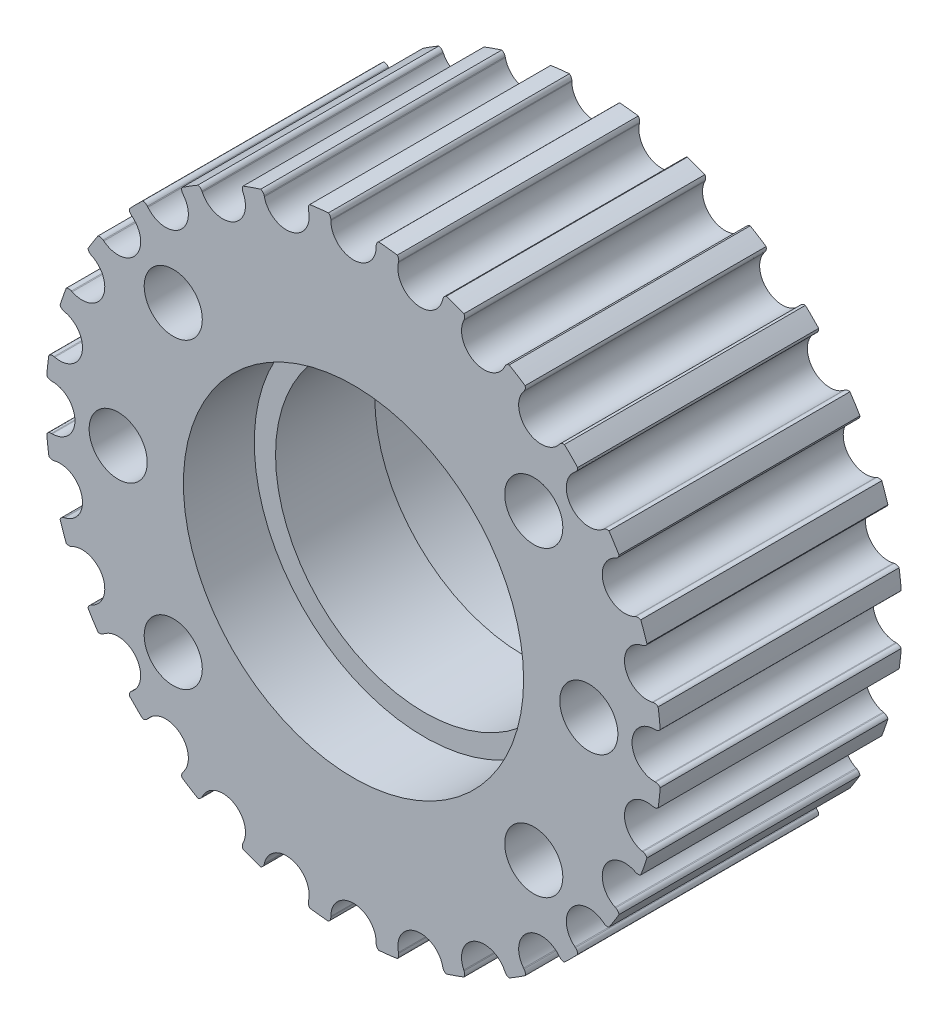
SolidWorks part; units mm, degrees
ref_plane "Front Plane" through (0, 0, 0) normal (0, 0, 1) x (1, 0, 0)
ref_plane "Top Plane" through (0, 0, 0) normal (0, 1, 0) x (1, 0, 0)
ref_plane "Right Plane" through (0, 0, 0) normal (1, 0, 0) x (0, 0, -1)
sketch "Sketch1" plane through (0, 0, 0) normal (0, 0, 1) x (1, 0, 0)
  line L0 (3.182, 21.1317) -> (3.1687, 21.0733)
  line L1 (6.2885, 20.3612) -> (6.3018, 20.4197)
  line L2 (7.8045, 19.8939) -> (7.7785, 19.8398)
  line L3 (10.6616, 18.4514) -> (10.6876, 18.5054)
  line L4 (-1.6, 21.31) -> (-1.6, 21.25)
  line L5 (1.6, 21.25) -> (1.6, 21.31)
  line L6 (12.0356, 17.6584) -> (11.9982, 17.6115)
  line L7 (14.5001, 15.6163) -> (14.5375, 15.6632)
  line L8 (15.6632, 14.5375) -> (15.6163, 14.5001)
  line L9 (17.6115, 11.9982) -> (17.6584, 12.0356)
  line L10 (18.5054, 10.6876) -> (18.4514, 10.6616)
  line L11 (19.8398, 7.7785) -> (19.8939, 7.8045)
  line L12 (20.4197, 6.3018) -> (20.3612, 6.2885)
  line L13 (21.0733, 3.1687) -> (21.1317, 3.182)
  line L14 (21.31, 1.6) -> (21.25, 1.6)
  line L15 (21.25, -1.6) -> (21.31, -1.6)
  line L16 (21.1317, -3.182) -> (21.0733, -3.1687)
  line L17 (20.3612, -6.2885) -> (20.4197, -6.3018)
  line L18 (19.8939, -7.8045) -> (19.8398, -7.7785)
  line L19 (18.4514, -10.6616) -> (18.5054, -10.6876)
  line L20 (17.6584, -12.0356) -> (17.6115, -11.9982)
  line L21 (15.6163, -14.5001) -> (15.6632, -14.5375)
  line L22 (14.5375, -15.6632) -> (14.5001, -15.6163)
  line L23 (11.9982, -17.6115) -> (12.0356, -17.6584)
  line L24 (10.6876, -18.5054) -> (10.6616, -18.4514)
  line L25 (7.7785, -19.8398) -> (7.8045, -19.8939)
  line L26 (6.3018, -20.4197) -> (6.2885, -20.3612)
  line L27 (3.1687, -21.0733) -> (3.182, -21.1317)
  line L28 (1.6, -21.31) -> (1.6, -21.25)
  line L29 (-1.6, -21.25) -> (-1.6, -21.31)
  line L30 (-3.182, -21.1317) -> (-3.1687, -21.0733)
  line L31 (-6.2885, -20.3612) -> (-6.3018, -20.4197)
  line L32 (-7.8045, -19.8939) -> (-7.7785, -19.8398)
  line L33 (-10.6616, -18.4514) -> (-10.6876, -18.5054)
  line L34 (-12.0356, -17.6584) -> (-11.9982, -17.6115)
  line L35 (-14.5001, -15.6163) -> (-14.5375, -15.6632)
  line L36 (-15.6632, -14.5375) -> (-15.6163, -14.5001)
  line L37 (-17.6115, -11.9982) -> (-17.6584, -12.0356)
  line L38 (-18.5054, -10.6876) -> (-18.4514, -10.6616)
  line L39 (-19.8398, -7.7785) -> (-19.8939, -7.8045)
  line L40 (-20.4197, -6.3018) -> (-20.3612, -6.2885)
  line L41 (-21.0733, -3.1687) -> (-21.1317, -3.182)
  line L42 (-21.31, -1.6) -> (-21.25, -1.6)
  line L43 (-21.25, 1.6) -> (-21.31, 1.6)
  line L44 (-21.1317, 3.182) -> (-21.0733, 3.1687)
  line L45 (-20.3612, 6.2885) -> (-20.4197, 6.3018)
  line L46 (-19.8939, 7.8045) -> (-19.8398, 7.7785)
  line L47 (-18.4514, 10.6616) -> (-18.5054, 10.6876)
  line L48 (-17.6584, 12.0356) -> (-17.6115, 11.9982)
  line L49 (-15.6163, 14.5001) -> (-15.6632, 14.5375)
  line L50 (-14.5375, 15.6632) -> (-14.5001, 15.6163)
  line L51 (-11.9982, 17.6115) -> (-12.0356, 17.6584)
  line L52 (-10.6876, 18.5054) -> (-10.6616, 18.4514)
  line L53 (-7.7785, 19.8398) -> (-7.8045, 19.8939)
  line L54 (-6.3018, 20.4197) -> (-6.2885, 20.3612)
  line L55 (-3.1687, 21.0733) -> (-3.182, 21.1317)
  arc A2 (-1.7706, 21.6377) -> (-3.0886, 21.4892) centre (0, 0) ccw
  arc A3 (3.0886, 21.4892) -> (1.7706, 21.6377) centre (0, 0) ccw
  arc A4 (3.0886, 21.4892) -> (1.7706, 21.6377) centre (0, 0) ccw
  arc A5 (7.793, 20.2631) -> (6.541, 20.7012) centre (0, 0) ccw
  arc A6 (6.541, 20.7012) -> (6.3018, 20.4197) centre (6.6918, 20.3307) ccw
  arc A7 (6.541, 20.7012) -> (3.0886, 21.4892) centre (0, 0) ccw
  arc A8 (1.7706, 21.6377) -> (1.6, 21.31) centre (2, 21.31) ccw
  arc A9 (1.7706, 21.6377) -> (-1.7706, 21.6377) centre (0, 0) ccw
  arc A10 (-1.6, 21.31) -> (-1.7706, 21.6377) centre (-2, 21.31) ccw
  arc A11 (-1.6, 21.25) -> (1.6, 21.25) centre (0, 21.25) ccw
  arc A12 (3.182, 21.1317) -> (3.0886, 21.4892) centre (2.7921, 21.2208) ccw
  arc A13 (3.1687, 21.0733) -> (6.2885, 20.3612) centre (4.7286, 20.7172) ccw
  arc A14 (7.793, 20.2631) -> (6.541, 20.7012) centre (0, 0) ccw
  arc A15 (12.1066, 18.021) -> (10.9835, 18.7266) centre (0, 0) ccw
  arc A16 (10.9835, 18.7266) -> (10.6876, 18.5054) centre (11.048, 18.3319) ccw
  arc A17 (10.9835, 18.7266) -> (7.793, 20.2631) centre (0, 0) ccw
  arc A18 (7.8045, 19.8939) -> (7.793, 20.2631) centre (7.4441, 20.0674) ccw
  arc A19 (7.7785, 19.8398) -> (10.6616, 18.4514) centre (9.22, 19.1456) ccw
  arc A20 (12.1066, 18.021) -> (10.9835, 18.7266) centre (0, 0) ccw
  arc A21 (15.8131, 14.8752) -> (14.8752, 15.8131) centre (0, 0) ccw
  arc A22 (14.8752, 15.8131) -> (14.5375, 15.6632) centre (14.8502, 15.4138) ccw
  arc A23 (14.8752, 15.8131) -> (12.1066, 18.021) centre (0, 0) ccw
  arc A24 (12.0356, 17.6584) -> (12.1066, 18.021) centre (11.7229, 17.9078) ccw
  arc A25 (11.9982, 17.6115) -> (14.5001, 15.6163) centre (13.2492, 16.6139) ccw
  arc A26 (15.8131, 14.8752) -> (14.8752, 15.8131) centre (0, 0) ccw
  arc A27 (18.7266, 10.9835) -> (18.021, 12.1066) centre (0, 0) ccw
  arc A28 (18.021, 12.1066) -> (17.6584, 12.0356) centre (17.9078, 11.7229) ccw
  arc A29 (18.021, 12.1066) -> (15.8131, 14.8752) centre (0, 0) ccw
  arc A30 (15.6632, 14.5375) -> (15.8131, 14.8752) centre (15.4138, 14.8502) ccw
  arc A31 (15.6163, 14.5001) -> (17.6115, 11.9982) centre (16.6139, 13.2492) ccw
  arc A32 (18.7266, 10.9835) -> (18.021, 12.1066) centre (0, 0) ccw
  arc A33 (20.7012, 6.541) -> (20.2631, 7.793) centre (0, 0) ccw
  arc A34 (20.2631, 7.793) -> (19.8939, 7.8045) centre (20.0674, 7.4441) ccw
  arc A35 (20.2631, 7.793) -> (18.7266, 10.9835) centre (0, 0) ccw
  arc A36 (18.5054, 10.6876) -> (18.7266, 10.9835) centre (18.3319, 11.048) ccw
  arc A37 (18.4514, 10.6616) -> (19.8398, 7.7785) centre (19.1456, 9.22) ccw
  arc A38 (20.7012, 6.541) -> (20.2631, 7.793) centre (0, 0) ccw
  arc A39 (21.6377, 1.7706) -> (21.4892, 3.0886) centre (0, 0) ccw
  arc A40 (21.4892, 3.0886) -> (21.1317, 3.182) centre (21.2208, 2.7921) ccw
  arc A41 (21.4892, 3.0886) -> (20.7012, 6.541) centre (0, 0) ccw
  arc A42 (20.4197, 6.3018) -> (20.7012, 6.541) centre (20.3307, 6.6918) ccw
  arc A43 (20.3612, 6.2885) -> (21.0733, 3.1687) centre (20.7172, 4.7286) ccw
  arc A44 (21.6377, 1.7706) -> (21.4892, 3.0886) centre (0, 0) ccw
  arc A45 (21.4892, -3.0886) -> (21.6377, -1.7706) centre (0, 0) ccw
  arc A46 (21.6377, -1.7706) -> (21.31, -1.6) centre (21.31, -2) ccw
  arc A47 (21.6377, -1.7706) -> (21.6377, 1.7706) centre (0, 0) ccw
  arc A48 (21.31, 1.6) -> (21.6377, 1.7706) centre (21.31, 2) ccw
  arc A49 (21.25, 1.6) -> (21.25, -1.6) centre (21.25, 0) ccw
  arc A50 (21.4892, -3.0886) -> (21.6377, -1.7706) centre (0, 0) ccw
  arc A51 (20.2631, -7.793) -> (20.7012, -6.541) centre (0, 0) ccw
  arc A52 (20.7012, -6.541) -> (20.4197, -6.3018) centre (20.3307, -6.6918) ccw
  arc A53 (20.7012, -6.541) -> (21.4892, -3.0886) centre (0, 0) ccw
  arc A54 (21.1317, -3.182) -> (21.4892, -3.0886) centre (21.2208, -2.7921) ccw
  arc A55 (21.0733, -3.1687) -> (20.3612, -6.2885) centre (20.7172, -4.7286) ccw
  arc A56 (20.2631, -7.793) -> (20.7012, -6.541) centre (0, 0) ccw
  arc A57 (18.021, -12.1066) -> (18.7266, -10.9835) centre (0, 0) ccw
  arc A58 (18.7266, -10.9835) -> (18.5054, -10.6876) centre (18.3319, -11.048) ccw
  arc A59 (18.7266, -10.9835) -> (20.2631, -7.793) centre (0, 0) ccw
  arc A60 (19.8939, -7.8045) -> (20.2631, -7.793) centre (20.0674, -7.4441) ccw
  arc A61 (19.8398, -7.7785) -> (18.4514, -10.6616) centre (19.1456, -9.22) ccw
  arc A62 (18.021, -12.1066) -> (18.7266, -10.9835) centre (0, 0) ccw
  arc A63 (14.8752, -15.8131) -> (15.8131, -14.8752) centre (0, 0) ccw
  arc A64 (15.8131, -14.8752) -> (15.6632, -14.5375) centre (15.4138, -14.8502) ccw
  arc A65 (15.8131, -14.8752) -> (18.021, -12.1066) centre (0, 0) ccw
  arc A66 (17.6584, -12.0356) -> (18.021, -12.1066) centre (17.9078, -11.7229) ccw
  arc A67 (17.6115, -11.9982) -> (15.6163, -14.5001) centre (16.6139, -13.2492) ccw
  arc A68 (14.8752, -15.8131) -> (15.8131, -14.8752) centre (0, 0) ccw
  arc A69 (10.9835, -18.7266) -> (12.1066, -18.021) centre (0, 0) ccw
  arc A70 (12.1066, -18.021) -> (12.0356, -17.6584) centre (11.7229, -17.9078) ccw
  arc A71 (12.1066, -18.021) -> (14.8752, -15.8131) centre (0, 0) ccw
  arc A72 (14.5375, -15.6632) -> (14.8752, -15.8131) centre (14.8502, -15.4138) ccw
  arc A73 (14.5001, -15.6163) -> (11.9982, -17.6115) centre (13.2492, -16.6139) ccw
  arc A74 (10.9835, -18.7266) -> (12.1066, -18.021) centre (0, 0) ccw
  arc A75 (6.541, -20.7012) -> (7.793, -20.2631) centre (0, 0) ccw
  arc A76 (7.793, -20.2631) -> (7.8045, -19.8939) centre (7.4441, -20.0674) ccw
  arc A77 (7.793, -20.2631) -> (10.9835, -18.7266) centre (0, 0) ccw
  arc A78 (10.6876, -18.5054) -> (10.9835, -18.7266) centre (11.048, -18.3319) ccw
  arc A79 (10.6616, -18.4514) -> (7.7785, -19.8398) centre (9.22, -19.1456) ccw
  arc A80 (6.541, -20.7012) -> (7.793, -20.2631) centre (0, 0) ccw
  arc A81 (1.7706, -21.6377) -> (3.0886, -21.4892) centre (0, 0) ccw
  arc A82 (3.0886, -21.4892) -> (3.182, -21.1317) centre (2.7921, -21.2208) ccw
  arc A83 (3.0886, -21.4892) -> (6.541, -20.7012) centre (0, 0) ccw
  arc A84 (6.3018, -20.4197) -> (6.541, -20.7012) centre (6.6918, -20.3307) ccw
  arc A85 (6.2885, -20.3612) -> (3.1687, -21.0733) centre (4.7286, -20.7172) ccw
  arc A86 (1.7706, -21.6377) -> (3.0886, -21.4892) centre (0, 0) ccw
  arc A87 (-3.0886, -21.4892) -> (-1.7706, -21.6377) centre (0, 0) ccw
  arc A88 (-1.7706, -21.6377) -> (-1.6, -21.31) centre (-2, -21.31) ccw
  arc A89 (-1.7706, -21.6377) -> (1.7706, -21.6377) centre (0, 0) ccw
  arc A90 (1.6, -21.31) -> (1.7706, -21.6377) centre (2, -21.31) ccw
  arc A91 (1.6, -21.25) -> (-1.6, -21.25) centre (0, -21.25) ccw
  arc A92 (-3.0886, -21.4892) -> (-1.7706, -21.6377) centre (0, 0) ccw
  arc A93 (-7.793, -20.2631) -> (-6.541, -20.7012) centre (0, 0) ccw
  arc A94 (-6.541, -20.7012) -> (-6.3018, -20.4197) centre (-6.6918, -20.3307) ccw
  arc A95 (-6.541, -20.7012) -> (-3.0886, -21.4892) centre (0, 0) ccw
  arc A96 (-3.182, -21.1317) -> (-3.0886, -21.4892) centre (-2.7921, -21.2208) ccw
  arc A97 (-3.1687, -21.0733) -> (-6.2885, -20.3612) centre (-4.7286, -20.7172) ccw
  arc A98 (-7.793, -20.2631) -> (-6.541, -20.7012) centre (0, 0) ccw
  arc A99 (-12.1066, -18.021) -> (-10.9835, -18.7266) centre (0, 0) ccw
  arc A100 (-10.9835, -18.7266) -> (-10.6876, -18.5054) centre (-11.048, -18.3319) ccw
  arc A101 (-10.9835, -18.7266) -> (-7.793, -20.2631) centre (0, 0) ccw
  arc A102 (-7.8045, -19.8939) -> (-7.793, -20.2631) centre (-7.4441, -20.0674) ccw
  arc A103 (-7.7785, -19.8398) -> (-10.6616, -18.4514) centre (-9.22, -19.1456) ccw
  arc A104 (-12.1066, -18.021) -> (-10.9835, -18.7266) centre (0, 0) ccw
  arc A105 (-15.8131, -14.8752) -> (-14.8752, -15.8131) centre (0, 0) ccw
  arc A106 (-14.8752, -15.8131) -> (-14.5375, -15.6632) centre (-14.8502, -15.4138) ccw
  arc A107 (-14.8752, -15.8131) -> (-12.1066, -18.021) centre (0, 0) ccw
  arc A108 (-12.0356, -17.6584) -> (-12.1066, -18.021) centre (-11.7229, -17.9078) ccw
  arc A109 (-11.9982, -17.6115) -> (-14.5001, -15.6163) centre (-13.2492, -16.6139) ccw
  arc A110 (-15.8131, -14.8752) -> (-14.8752, -15.8131) centre (0, 0) ccw
  arc A111 (-18.7266, -10.9835) -> (-18.021, -12.1066) centre (0, 0) ccw
  arc A112 (-18.021, -12.1066) -> (-17.6584, -12.0356) centre (-17.9078, -11.7229) ccw
  arc A113 (-18.021, -12.1066) -> (-15.8131, -14.8752) centre (0, 0) ccw
  arc A114 (-15.6632, -14.5375) -> (-15.8131, -14.8752) centre (-15.4138, -14.8502) ccw
  arc A115 (-15.6163, -14.5001) -> (-17.6115, -11.9982) centre (-16.6139, -13.2492) ccw
  arc A116 (-18.7266, -10.9835) -> (-18.021, -12.1066) centre (0, 0) ccw
  arc A117 (-20.7012, -6.541) -> (-20.2631, -7.793) centre (0, 0) ccw
  arc A118 (-20.2631, -7.793) -> (-19.8939, -7.8045) centre (-20.0674, -7.4441) ccw
  arc A119 (-20.2631, -7.793) -> (-18.7266, -10.9835) centre (0, 0) ccw
  arc A120 (-18.5054, -10.6876) -> (-18.7266, -10.9835) centre (-18.3319, -11.048) ccw
  arc A121 (-18.4514, -10.6616) -> (-19.8398, -7.7785) centre (-19.1456, -9.22) ccw
  arc A122 (-20.7012, -6.541) -> (-20.2631, -7.793) centre (0, 0) ccw
  arc A123 (-21.6377, -1.7706) -> (-21.4892, -3.0886) centre (0, 0) ccw
  arc A124 (-21.4892, -3.0886) -> (-21.1317, -3.182) centre (-21.2208, -2.7921) ccw
  arc A125 (-21.4892, -3.0886) -> (-20.7012, -6.541) centre (0, 0) ccw
  arc A126 (-20.4197, -6.3018) -> (-20.7012, -6.541) centre (-20.3307, -6.6918) ccw
  arc A127 (-20.3612, -6.2885) -> (-21.0733, -3.1687) centre (-20.7172, -4.7286) ccw
  arc A128 (-21.6377, -1.7706) -> (-21.4892, -3.0886) centre (0, 0) ccw
  arc A129 (-21.4892, 3.0886) -> (-21.6377, 1.7706) centre (0, 0) ccw
  arc A130 (-21.6377, 1.7706) -> (-21.31, 1.6) centre (-21.31, 2) ccw
  arc A131 (-21.6377, 1.7706) -> (-21.6377, -1.7706) centre (0, 0) ccw
  arc A132 (-21.31, -1.6) -> (-21.6377, -1.7706) centre (-21.31, -2) ccw
  arc A133 (-21.25, -1.6) -> (-21.25, 1.6) centre (-21.25, 0) ccw
  arc A134 (-21.4892, 3.0886) -> (-21.6377, 1.7706) centre (0, 0) ccw
  arc A135 (-20.2631, 7.793) -> (-20.7012, 6.541) centre (0, 0) ccw
  arc A136 (-20.7012, 6.541) -> (-20.4197, 6.3018) centre (-20.3307, 6.6918) ccw
  arc A137 (-20.7012, 6.541) -> (-21.4892, 3.0886) centre (0, 0) ccw
  arc A138 (-21.1317, 3.182) -> (-21.4892, 3.0886) centre (-21.2208, 2.7921) ccw
  arc A139 (-21.0733, 3.1687) -> (-20.3612, 6.2885) centre (-20.7172, 4.7286) ccw
  arc A140 (-20.2631, 7.793) -> (-20.7012, 6.541) centre (0, 0) ccw
  arc A141 (-18.021, 12.1066) -> (-18.7266, 10.9835) centre (0, 0) ccw
  arc A142 (-18.7266, 10.9835) -> (-18.5054, 10.6876) centre (-18.3319, 11.048) ccw
  arc A143 (-18.7266, 10.9835) -> (-20.2631, 7.793) centre (0, 0) ccw
  arc A144 (-19.8939, 7.8045) -> (-20.2631, 7.793) centre (-20.0674, 7.4441) ccw
  arc A145 (-19.8398, 7.7785) -> (-18.4514, 10.6616) centre (-19.1456, 9.22) ccw
  arc A146 (-18.021, 12.1066) -> (-18.7266, 10.9835) centre (0, 0) ccw
  arc A147 (-14.8752, 15.8131) -> (-15.8131, 14.8752) centre (0, 0) ccw
  arc A148 (-15.8131, 14.8752) -> (-15.6632, 14.5375) centre (-15.4138, 14.8502) ccw
  arc A149 (-15.8131, 14.8752) -> (-18.021, 12.1066) centre (0, 0) ccw
  arc A150 (-17.6584, 12.0356) -> (-18.021, 12.1066) centre (-17.9078, 11.7229) ccw
  arc A151 (-17.6115, 11.9982) -> (-15.6163, 14.5001) centre (-16.6139, 13.2492) ccw
  arc A152 (-14.8752, 15.8131) -> (-15.8131, 14.8752) centre (0, 0) ccw
  arc A153 (-10.9835, 18.7266) -> (-12.1066, 18.021) centre (0, 0) ccw
  arc A154 (-12.1066, 18.021) -> (-12.0356, 17.6584) centre (-11.7229, 17.9078) ccw
  arc A155 (-12.1066, 18.021) -> (-14.8752, 15.8131) centre (0, 0) ccw
  arc A156 (-14.5375, 15.6632) -> (-14.8752, 15.8131) centre (-14.8502, 15.4138) ccw
  arc A157 (-14.5001, 15.6163) -> (-11.9982, 17.6115) centre (-13.2492, 16.6139) ccw
  arc A158 (-10.9835, 18.7266) -> (-12.1066, 18.021) centre (0, 0) ccw
  arc A159 (-6.541, 20.7012) -> (-7.793, 20.2631) centre (0, 0) ccw
  arc A160 (-7.793, 20.2631) -> (-7.8045, 19.8939) centre (-7.4441, 20.0674) ccw
  arc A161 (-7.793, 20.2631) -> (-10.9835, 18.7266) centre (0, 0) ccw
  arc A162 (-10.6876, 18.5054) -> (-10.9835, 18.7266) centre (-11.048, 18.3319) ccw
  arc A163 (-10.6616, 18.4514) -> (-7.7785, 19.8398) centre (-9.22, 19.1456) ccw
  arc A164 (-6.541, 20.7012) -> (-7.793, 20.2631) centre (0, 0) ccw
  arc A165 (-1.7706, 21.6377) -> (-3.0886, 21.4892) centre (0, 0) ccw
  arc A166 (-3.0886, 21.4892) -> (-3.182, 21.1317) centre (-2.7921, 21.2208) ccw
  arc A167 (-3.0886, 21.4892) -> (-6.541, 20.7012) centre (0, 0) ccw
  arc A168 (-6.3018, 20.4197) -> (-6.541, 20.7012) centre (-6.6918, 20.3307) ccw
  arc A169 (-6.2885, 20.3612) -> (-3.1687, 21.0733) centre (-4.7286, 20.7172) ccw
  point P369 (0, 0)
  dimension "D1" = 28
extrude "Boss-Extrude1" add sketch "Sketch1" along normal blind 17 contours A169 L54 A168 A159 A160 L53 A163 L52 A162 A153 A154 L51 A157 L50 A156 A147 A148 L49 A151 L48 A150 A141 A142 L47 A145 L46 A144 A135 A136 L45 A139 L44 A138 A129 A130 L43 A133 L42 A132 A123 A124 L41 A127 L40 A126 A117 A118 L39 A121 L38 A120 region at (0, 0, 0)
sketch "Sketch2" plane through (0, 0, 0) normal (0, 0, -1) x (-1, 0, 0)
  line L0 (12.7163, 10.6703) -> (0, 0) construction
  line L1 (-7.1138, 0) -> (34.7835, 0) construction
  circle A2 centre (0, 0) radius 16.6 construction
  circle A3 centre (16.6, 0) radius 2.05
  arc A4 (21.25, 1.6) -> (21.25, -1.6) centre (21.25, 0) ccw construction
  circle A5 centre (12.7163, 10.6703) radius 2.05
  circle A6 centre (12.7163, -10.6703) radius 2.05
  circle A7 centre (0, 0) radius 12
  circle A8 centre (0, 0) radius 7.5 construction
  circle A9 centre (0, 0) radius 10.5
  circle A10 centre (0, 0) radius 13.5 construction
  dimension "D1" = 4.1
  dimension "D2" = 1
  dimension "D3" = 4.1
  dimension "D5" = 24
  dimension "D6" = 15
  dimension "D7" = 21
  dimension "D8" = 27
  dimension "D4" = 40
extrude "Cut-Extrude1" cut sketch "Sketch2" against normal up to surface (17 mm away) contours A5 | A3 | A6 | A9 | A3 region at (-16.6, 0, 0) region at (-12.7163, 10.6703, 0) region at (-12.7163, -10.6703, 0) region at (0, 0, 0) up to face at (0, 0, 17)
extrude "Cut-Extrude2" cut sketch "Sketch2<4>" against normal blind 5 contours A7 A9 region at (11.6606, 0, 0)
sketch "Sketch2<4>" plane through (0, 0, 0) normal (0, 0, -1) x (-1, 0, 0) same geometry as "Sketch2"
extrude "Cut-Extrude3" cut sketch "Sketch2<5>" along normal blind 5 from surface starting at face at (10.5, 0, 17)
sketch "Sketch2<5>" plane through (0, 0, 0) normal (0, 0, -1) x (-1, 0, 0) same geometry as "Sketch2"
mirror "Mirror1" about plane through (0, 0, 0) normal (1, 0, 0) of "Cut-Extrude1"
sketch "Sketch3" plane through (0, 0, 17) normal (0, 0, 1) x (1, 0, 0)
  circle A0 centre (0, 0) radius 13.5
  dimension "D1" = 27
